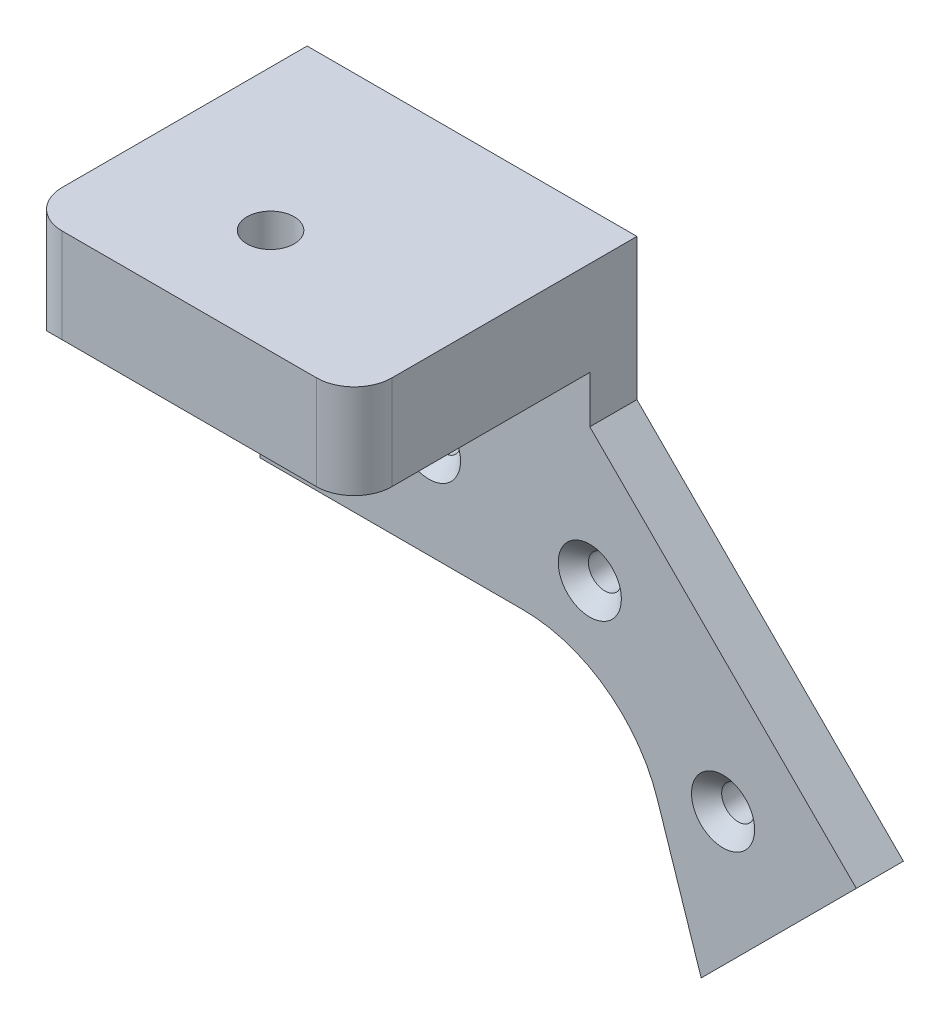
SolidWorks part; units mm, degrees
ref_plane "Front Plane" through (0, 0, 0) normal (0, 0, 1) x (1, 0, 0)
ref_plane "Top Plane" through (0, 0, 0) normal (0, 1, 0) x (1, 0, 0)
ref_plane "Right Plane" through (0, 0, 0) normal (1, 0, 0) x (0, 0, -1)
sketch "Sketch1" plane through (0, 0, 0) normal (0, 0, 1) x (1, 0, 0)
  line L0 (17.5, 27.5) -> (17.5, 12.5)
  line L5 (-17.5, 27.5) -> (17.5, 27.5)
  line L6 (-17.5, 27.5) -> (-17.5, -27.5)
  line L7 (-17.5, -27.5) -> (17.5, -27.5)
  line L9 (17.5, 12.5) -> (45.7843, -15.7843)
  line L10 (-17.5, -27.5) -> (17.5, 27.5) construction
  line L11 (45.7843, -15.7843) -> (25.7843, -35.7843)
  line L12 (25.7843, -35.7843) -> (17.5, -27.5)
  point P0 (0, 0)
  dimension "D1" = 45
  dimension "D2" = 55
  dimension "D3" = 35
  dimension "D4" = 40
  dimension "D5" = 15
extrude "Boss-Extrude1" add sketch "Sketch1" along normal blind 5
sketch "Sketch3" plane through (0, 0, 5) normal (0, 0, 1) x (1, 0, 0)
  line L0 (17.5, 12.5) -> (17.5, 27.5) construction
  line L1 (-17.5, 27.5) -> (17.5, 27.5)
  line L2 (-17.5, 27.5) -> (-17.5, 17.5)
  line L3 (-17.5, 17.5) -> (17.5, 17.5)
  line L4 (17.5, 27.5) -> (17.5, 17.5)
  dimension "D1" = 10
extrude "Boss-Extrude2" add sketch "Sketch3" along normal blind 25
sketch "Sketch4" plane through (0, 27.5, 0) normal (0, 1, 0) x (1, 0, 0)
  line L0 (-17.5, -30) -> (-17.5, 0) construction
  line L1 (17.5, -30) -> (-17.5, -30) construction
  line L2 (17.5, -30) -> (17.5, -5) construction
  line L3 (17.5, -5) -> (-17.5, -5) construction
  line L4 (-17.5, -30) -> (-17.5, -5) construction
  line L5 (17.5, -30) -> (17.5, 0) construction
  line L6 (-17.5, 0) -> (17.5, 0) construction
  line L7 (-17.5, 0) -> (-17.5, 5) construction
  line L8 (-17.5, 5) -> (17.5, 5) construction
  line L9 (17.5, 0) -> (17.5, 5) construction
  circle A0 centre (-2.5, -18.88) radius 2.5
  circle A1 centre (-2.5, -18.88) radius 6.5 construction
  dimension "D3" = 13
  dimension "D4" = 5
  dimension "D1" = 25
  dimension "D2" = 5
  dimension "D5" = 23.88
  dimension "D6" = 20
extrude "Cut-Extrude1" cut sketch "Sketch4" against normal through all
sketch "Sketch6" plane through (-17.5, 0, 0) normal (-1, 0, 0) x (0, 0, 1)
  line L0 (30, 17.5) -> (5, -7.5)
  line L1 (5, 17.5) -> (5, -27.5) construction
  dimension "D1" = 45
rib "Rib1" sketch "Sketch6" sketch "Sketch6" thickness 5 extrusion direction parallel to sketch draft on no parameters "D1"=5
sketch "Sketch7" plane through (0, 0, 5) normal (0, 0, 1) x (1, 0, 0)
  line L0 (24.6747, -18.1589) -> (29.3198, -32.2487)
  line L1 (-17.5, -7.8553) -> (10.4289, -7.8553)
  line L2 (-17.5, -7.8553) -> (-17.5, -27.5)
  line L3 (-17.5, -7.5) -> (-17.5, -27.5) construction
  line L4 (-17.5, -27.5) -> (17.5, -27.5) construction
  line L5 (17.5, 27.5) -> (-17.5, 27.5) construction
  line L6 (25.7843, -35.7843) -> (45.7843, -15.7843) construction
  line L7 (-17.5, -27.5) -> (25.7843, -35.7843)
  line L8 (25.7843, -35.7843) -> (29.3198, -32.2487)
  arc A0 (24.6747, -18.1589) -> (10.4289, -7.8553) centre (10.4289, -22.8553) ccw
  circle A1 centre (10.4289, -22.8553) radius 14 construction
  point P16 (31.7397, -29.8289)
  dimension "D1" = 1
  dimension "D2" = 5
extrude "Cut-Extrude2" cut sketch "Sketch7" against normal up to vertex (5 mm away) up to point (-17.5, -27.5, 0)
sketch "Sketch8" plane through (0, 17.5, 0) normal (0, -1, 0) x (-1, 0, 0)
  line L1 (-2.2343, -18.88) -> (0.1329, -22.98)
  line L2 (0.1329, -22.98) -> (4.8671, -22.98)
  line L3 (4.8671, -22.98) -> (7.2343, -18.88)
  line L4 (7.2343, -18.88) -> (4.8671, -14.78)
  line L5 (4.8671, -14.78) -> (0.1329, -14.78)
  line L6 (0.1329, -14.78) -> (-2.2343, -18.88)
  circle A0 centre (2.5, -18.88) radius 4.1 construction
  dimension "D1" = 8.2
extrude "Cut-Extrude3" cut sketch "Sketch8" against normal blind 5
fillet "Fillet1" radius 4 2 edges at (-17.5, 22.5, 30) (17.5, 22.5, 30)
sketch "Sketch9" plane through (0, 0, 5) normal (0, 0, 1) x (1, 0, 0)
  line L0 (17.5, -1.6421) -> (24.5711, 5.4289) construction
  line L1 (45.7843, -15.7843) -> (17.5, 12.5) construction
  line L2 (31.6421, -15.7843) -> (38.7132, -8.7132) construction
  line L3 (29.3198, -32.2487) -> (45.7843, -15.7843) construction
  line L4 (17.5, 12.5) -> (-2.8553, -7.8553) construction
  line L5 (10.4289, -7.8553) -> (-17.5, -7.8553) construction
  line L6 (17.5, 12.5) -> (-17.5, 12.5) construction
  line L7 (-17.5, 13.5) -> (-17.5, -7.5) construction
  circle A0 centre (17.5, -1.6421) radius 1.75
  circle A1 centre (31.6421, -15.7843) radius 1.75
  circle A2 centre (0.4289, 2.5) radius 1.75
  point P15 (-18.1204, 12.5)
  point P18 (-17.5, 12.5)
  dimension "D1" = 3.5
  dimension "D5" = 5
  dimension "D2" = 10
  dimension "D3" = 10
  dimension "D4" = 20
  dimension "D6" = 10
extrude "Cut-Extrude4" cut sketch "Sketch9" against normal through all
chamfer "Chamfer1" distance 1.6 angle 45 3 edges at (33.3921, -15.7843, 5) (19.25, -1.6421, 5) (2.1789, 2.5, 5)
